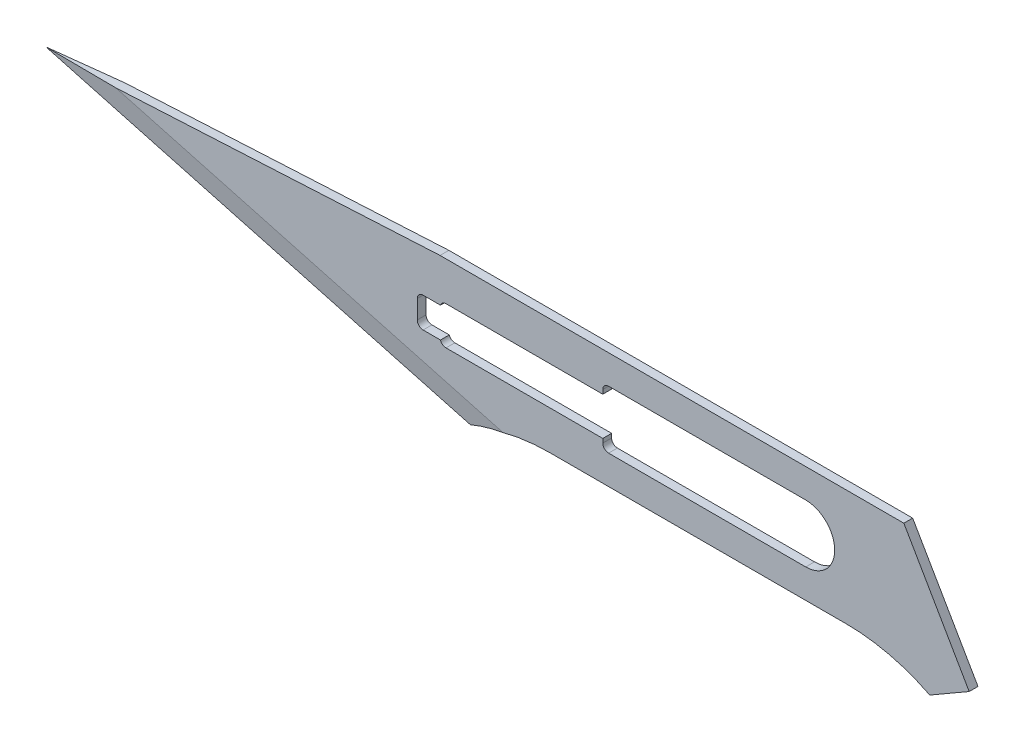
SolidWorks part; units mm, degrees
material "AISI Acier à outil type A2"
ref_plane "Plan de face" through (0, 0, 0) normal (0, 0, 1) x (1, 0, 0)
ref_plane "Plan de dessus" through (0, 0, 0) normal (0, 1, 0) x (1, 0, 0)
ref_plane "Plan de droite" through (0, 0, 0) normal (1, 0, 0) x (0, 0, -1)
sketch "Esquisse1" plane through (0, 0, 0) normal (0, 0, 1) x (1, 0, 0)
  line L0 (-17.1834, -0.9005) -> (0, 0)
  line L1 (0, 0) -> (20, 0)
  line L2 (20, 0) -> (22.8166, -4.8785)
  line L3 (22.8166, -4.8785) -> (21.1166, -5.86)
  line L4 (17.5082, -5) -> (4.725, -5)
  line L5 (1.1166, -5.86) -> (-17.1834, -0.9005)
  arc A0 (21.1166, -5.86) -> (17.5082, -5) centre (17.5082, -13) ccw
  arc A1 (4.725, -5) -> (1.1166, -5.86) centre (4.725, -13) ccw
  dimension "D7" = 8
  dimension "D1" = 5.86
  dimension "D2" = 40
  dimension "D3" = 20
  dimension "D4" = 5
  dimension "D5" = 60
  dimension "D6" = 1.7
  dimension "D8" = 3
  dimension "D9" = 20
extrude "Boss.-Extru.1" add sketch "Esquisse1" along normal mid plane 0.38
sketch "Esquisse2" plane through (0, 0, 0.19) normal (0, 0, 1) x (1, 0, 0)
  line L0 (-0.9834, -1.85) -> (0.0166, -1.85)
  line L1 (0.0166, -1.85) -> (0.0166, -1.675)
  line L2 (0.0166, -1.675) -> (7.0166, -1.675)
  line L3 (7.0166, -1.675) -> (7.0166, -1.25)
  line L4 (7.0166, -1.25) -> (15.7666, -1.25)
  line L5 (17.2437, -2.5) -> (1.1536, -2.5) construction
  line L6 (-0.9834, -1.85) -> (-0.9834, -3.15)
  line L7 (7.0166, -3.75) -> (15.7666, -3.75)
  line L8 (7.0166, -3.325) -> (7.0166, -3.75)
  line L9 (0.0166, -3.325) -> (7.0166, -3.325)
  line L10 (0.0166, -3.15) -> (0.0166, -3.325)
  line L11 (-0.9834, -3.15) -> (0.0166, -3.15)
  line L12 (15.7666, 0) -> (15.7666, -5) construction
  line L13 (20, 0) -> (0, 0) construction
  line L14 (4.725, -5) -> (17.5082, -5) construction
  arc A0 (15.7666, -1.25) -> (15.7666, -3.75) centre (15.7666, -2.5) cw
  point P12 (-0.9834, -2.5)
  dimension "D1" = 2.5
  dimension "D2" = 1.65
  dimension "D3" = 1.3
  dimension "D4" = 34.2
  dimension "D5" = 18
  dimension "D6" = 10
  dimension "D7" = 7
extrude "Enlèv. mat.-Extru.1" cut sketch "Esquisse2" against normal through all
fillet "Congé1" radius 0.25 6 edges at (7.0166, -3.75, 0) (7.0166, -1.25, 0) (0.0166, -3.325, 0) (0.0166, -1.675, 0) (-0.9834, -3.15, 0) (-0.9834, -1.85, 0)
ref_plane "Plan1" through (2.5197, -0.6828, 0) normal (-0.9652, 0.2616, 0) x (0, 0, 1)
sketch "Esquisse3" plane through (2.5197, -0.6828, 0) normal (-0.9652, 0.2616, 0) x (0, 0, 1)
  line L0 (0, -5.3639) -> (0.19, -4.3639)
  line L1 (0.19, -5.3639) -> (-0.19, -5.3639) construction
  line L2 (0.19, 0) -> (0.19, -5.3639) construction
  line L3 (0.19, -4.3639) -> (0.19, -5.5389)
  line L4 (0.19, -5.5389) -> (-0.19, -5.5389)
  line L5 (-0.19, -5.5389) -> (-0.19, -4.3639)
  line L6 (-0.19, 0) -> (-0.19, -5.3639) construction
  line L7 (-0.19, -4.3639) -> (0, -5.3639)
  dimension "D1" = 1
  dimension "D2" = 0.175
extrude "Enlèv. mat.-Extru.2" cut sketch "Esquisse3" against normal through all and the other way through all
